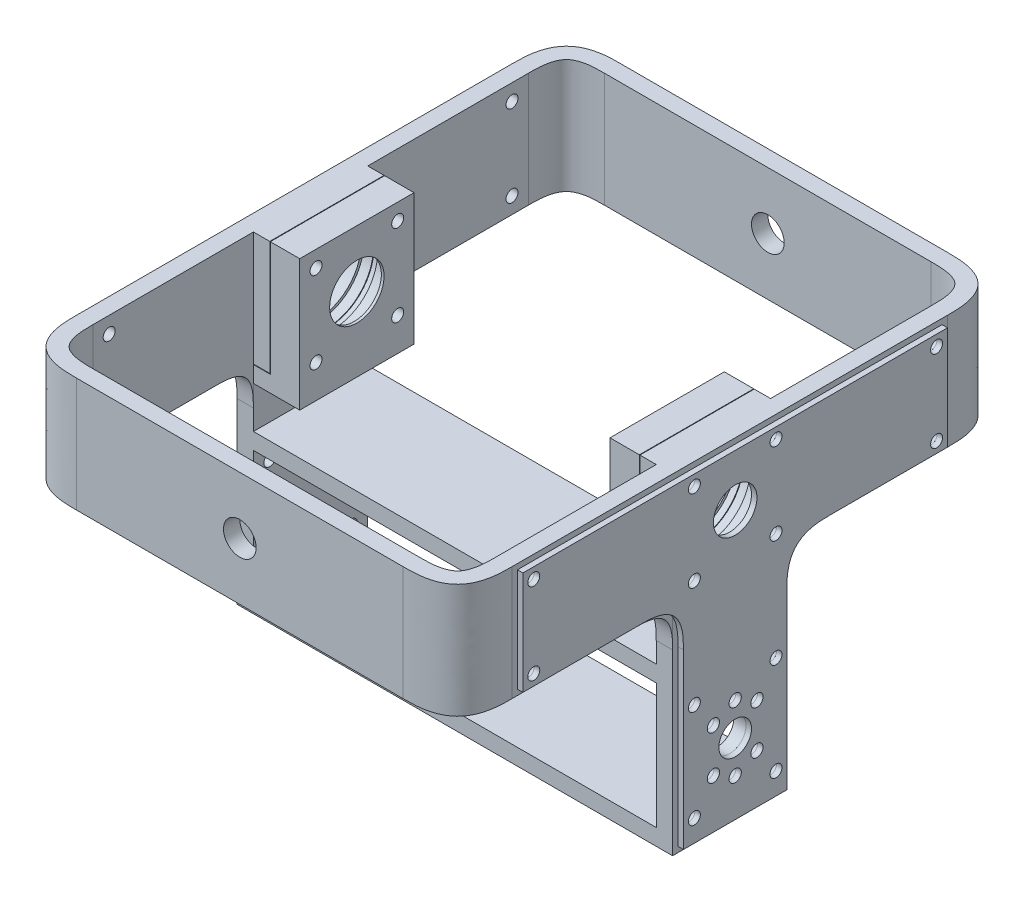
SolidWorks part; units mm, degrees
ref_plane "Front Plane" through (0, 0, 0) normal (0, 0, 1) x (1, 0, 0)
ref_plane "Top Plane" through (0, 0, 0) normal (0, 1, 0) x (1, 0, 0)
ref_plane "Right Plane" through (0, 0, 0) normal (1, 0, 0) x (0, 0, -1)
sketch "Sketch1" plane through (0, 0, 0) normal (0, 1, 0) x (1, 0, 0)
  line L1 (-80, 100) -> (80, 100)
  line L2 (-80, 100) -> (-80, -100)
  line L3 (-80, -100) -> (80, -100)
  line L4 (80, 100) -> (80, -100)
  point P4 (0, 100)
  point P6 (-80, 0)
  dimension "D1" = 200
  dimension "D2" = 160
extrude "Boss-Extrude1" add sketch "Sketch1" along normal mid plane 42
fillet "Fillet1" radius 20 4 edges at (-80, 0, 100) (80, 0, 100) (80, 0, -100) (-80, 0, -100) curvature continuous yes
sketch "Sketch2" plane through (0, 21, 0) normal (0, 1, 0) x (1, 0, 0)
  line L8 (-74, 80) -> (-74, -80)
  line L9 (-60, -94) -> (60, -94)
  line L10 (74, -80) -> (74, 80)
  line L11 (60, 94) -> (-60, 94)
  line L12 (-74, 80) -> (-74, -80)
  line L13 (-60, -94) -> (60, -94)
  line L14 (74, -80) -> (74, 80)
  line L15 (60, 94) -> (-60, 94)
  spline S9 degree 3 poles (-2071.4213, -155.8183) (-19.6568, -2.3852) (-75.4784, -45.3495) (-73.9199, -83.9583) (-73.84, -84.9423) (-73.6075, -86.4078) (-73.5109, -86.8945) (-73.2666, -87.8632) (-73.1188, -88.345) (-72.7604, -89.2755) (-72.5497, -89.7272) (-72.1629, -90.3744) (-72.0222, -90.5842) (-71.7196, -90.981) (-71.557, -91.1692) (-71.0313, -91.6999) (-70.625, -92.0093) (-69.7725, -92.5262) (-69.3225, -92.7397) (-68.3895, -93.1039) (-67.9093, -93.253) (-66.9456, -93.4997) (-66.4592, -93.5979) (-64.9892, -93.8351) (-63.9932, -93.9178) (-25.3456, -95.5031) (13.5346, -39.2005) (7.5566, -2091.7952) knots -4.636062 -4.636062 -4.636062 -4.636062 0.125 0.125 0.25 0.25 0.3125 0.3125 0.375 0.375 0.4375 0.4375 0.46875 0.46875 0.5 0.5 0.5625 0.5625 0.625 0.625 0.6875 0.6875 0.75 0.75 0.875 0.875 5.591292 5.591292 5.591292 5.591292 only from (-74, -80) to (-60, -94)
  spline S10 degree 3 poles (135.8183, -2091.4213) (-17.6148, -39.6568) (25.3495, -95.4784) (63.9583, -93.9199) (64.9423, -93.84) (66.4078, -93.6075) (66.8945, -93.5109) (67.8632, -93.2666) (68.345, -93.1188) (69.2755, -92.7604) (69.7272, -92.5497) (70.3744, -92.1629) (70.5842, -92.0222) (70.981, -91.7196) (71.1692, -91.557) (71.6999, -91.0313) (72.0093, -90.625) (72.5262, -89.7725) (72.7397, -89.3225) (73.1039, -88.3895) (73.253, -87.9093) (73.4997, -86.9456) (73.5979, -86.4592) (73.8351, -84.9892) (73.9178, -83.9932) (75.5031, -45.3456) (19.2005, -6.4654) (2071.7952, -12.4434) knots -4.636062 -4.636062 -4.636062 -4.636062 0.125 0.125 0.25 0.25 0.3125 0.3125 0.375 0.375 0.4375 0.4375 0.46875 0.46875 0.5 0.5 0.5625 0.5625 0.625 0.625 0.6875 0.6875 0.75 0.75 0.875 0.875 5.591292 5.591292 5.591292 5.591292 only from (60, -94) to (74, -80)
  spline S11 degree 3 poles (2071.4213, 155.8183) (19.6568, 2.3852) (75.4784, 45.3495) (73.9199, 83.9583) (73.84, 84.9423) (73.6075, 86.4078) (73.5109, 86.8945) (73.2666, 87.8632) (73.1188, 88.345) (72.7604, 89.2755) (72.5497, 89.7272) (72.1629, 90.3744) (72.0222, 90.5842) (71.7196, 90.981) (71.557, 91.1692) (71.0313, 91.6999) (70.625, 92.0093) (69.7725, 92.5262) (69.3225, 92.7397) (68.3895, 93.1039) (67.9093, 93.253) (66.9456, 93.4997) (66.4592, 93.5979) (64.9892, 93.8351) (63.9932, 93.9178) (25.3456, 95.5031) (-13.5346, 39.2005) (-7.5566, 2091.7952) knots -4.636062 -4.636062 -4.636062 -4.636062 0.125 0.125 0.25 0.25 0.3125 0.3125 0.375 0.375 0.4375 0.4375 0.46875 0.46875 0.5 0.5 0.5625 0.5625 0.625 0.625 0.6875 0.6875 0.75 0.75 0.875 0.875 5.591292 5.591292 5.591292 5.591292 only from (74, 80) to (60, 94)
  spline S12 degree 3 poles (-135.8183, 2091.4213) (17.6148, 39.6568) (-25.3495, 95.4784) (-63.9583, 93.9199) (-64.9423, 93.84) (-66.4078, 93.6075) (-66.8945, 93.5109) (-67.8632, 93.2666) (-68.345, 93.1188) (-69.2755, 92.7604) (-69.7272, 92.5497) (-70.3744, 92.1629) (-70.5842, 92.0222) (-70.981, 91.7196) (-71.1692, 91.557) (-71.6999, 91.0313) (-72.0093, 90.625) (-72.5262, 89.7725) (-72.7397, 89.3225) (-73.1039, 88.3895) (-73.253, 87.9093) (-73.4997, 86.9456) (-73.5979, 86.4592) (-73.8351, 84.9892) (-73.9178, 83.9932) (-75.5031, 45.3456) (-19.2005, 6.4654) (-2071.7952, 12.4434) knots -4.636062 -4.636062 -4.636062 -4.636062 0.125 0.125 0.25 0.25 0.3125 0.3125 0.375 0.375 0.4375 0.4375 0.46875 0.46875 0.5 0.5 0.5625 0.5625 0.625 0.625 0.6875 0.6875 0.75 0.75 0.875 0.875 5.591292 5.591292 5.591292 5.591292 only from (-60, 94) to (-74, 80)
  spline S13 degree 3 poles (-74, -80) (-74, -80.9914) (-73.9997, -81.9829) (-73.9199, -83.9583) (-73.84, -84.9423) (-73.6075, -86.4078) (-73.5109, -86.8945) (-73.2666, -87.8632) (-73.1188, -88.345) (-72.7604, -89.2755) (-72.5497, -89.7272) (-72.1629, -90.3744) (-72.0222, -90.5842) (-71.7196, -90.981) (-71.557, -91.1692) (-71.0313, -91.6999) (-70.625, -92.0093) (-69.7725, -92.5262) (-69.3225, -92.7397) (-68.3895, -93.1039) (-67.9093, -93.253) (-66.9456, -93.4997) (-66.4592, -93.5979) (-64.9892, -93.8351) (-63.9932, -93.9178) (-61.9975, -93.9997) (-60.9987, -94) (-60, -94) knots 0 0 0 0 0.125 0.125 0.25 0.25 0.3125 0.3125 0.375 0.375 0.4375 0.4375 0.46875 0.46875 0.5 0.5 0.5625 0.5625 0.625 0.625 0.6875 0.6875 0.75 0.75 0.875 0.875 1 1 1 1
  spline S14 degree 3 poles (60, -94) (60.9914, -94) (61.9829, -93.9997) (63.9583, -93.9199) (64.9423, -93.84) (66.4078, -93.6075) (66.8945, -93.5109) (67.8632, -93.2666) (68.345, -93.1188) (69.2755, -92.7604) (69.7272, -92.5497) (70.3744, -92.1629) (70.5842, -92.0222) (70.981, -91.7196) (71.1692, -91.557) (71.6999, -91.0313) (72.0093, -90.625) (72.5262, -89.7725) (72.7397, -89.3225) (73.1039, -88.3895) (73.253, -87.9093) (73.4997, -86.9456) (73.5979, -86.4592) (73.8351, -84.9892) (73.9178, -83.9932) (73.9997, -81.9975) (74, -80.9987) (74, -80) knots 0 0 0 0 0.125 0.125 0.25 0.25 0.3125 0.3125 0.375 0.375 0.4375 0.4375 0.46875 0.46875 0.5 0.5 0.5625 0.5625 0.625 0.625 0.6875 0.6875 0.75 0.75 0.875 0.875 1 1 1 1
  spline S15 degree 3 poles (74, 80) (74, 80.9914) (73.9997, 81.9829) (73.9199, 83.9583) (73.84, 84.9423) (73.6075, 86.4078) (73.5109, 86.8945) (73.2666, 87.8632) (73.1188, 88.345) (72.7604, 89.2755) (72.5497, 89.7272) (72.1629, 90.3744) (72.0222, 90.5842) (71.7196, 90.981) (71.557, 91.1692) (71.0313, 91.6999) (70.625, 92.0093) (69.7725, 92.5262) (69.3225, 92.7397) (68.3895, 93.1039) (67.9093, 93.253) (66.9456, 93.4997) (66.4592, 93.5979) (64.9892, 93.8351) (63.9932, 93.9178) (61.9975, 93.9997) (60.9987, 94) (60, 94) knots 0 0 0 0 0.125 0.125 0.25 0.25 0.3125 0.3125 0.375 0.375 0.4375 0.4375 0.46875 0.46875 0.5 0.5 0.5625 0.5625 0.625 0.625 0.6875 0.6875 0.75 0.75 0.875 0.875 1 1 1 1
  spline S16 degree 3 poles (-60, 94) (-60.9914, 94) (-61.9829, 93.9997) (-63.9583, 93.9199) (-64.9423, 93.84) (-66.4078, 93.6075) (-66.8945, 93.5109) (-67.8632, 93.2666) (-68.345, 93.1188) (-69.2755, 92.7604) (-69.7272, 92.5497) (-70.3744, 92.1629) (-70.5842, 92.0222) (-70.981, 91.7196) (-71.1692, 91.557) (-71.6999, 91.0313) (-72.0093, 90.625) (-72.5262, 89.7725) (-72.7397, 89.3225) (-73.1039, 88.3895) (-73.253, 87.9093) (-73.4997, 86.9456) (-73.5979, 86.4592) (-73.8351, 84.9892) (-73.9178, 83.9932) (-73.9997, 81.9975) (-74, 80.9987) (-74, 80) knots 0 0 0 0 0.125 0.125 0.25 0.25 0.3125 0.3125 0.375 0.375 0.4375 0.4375 0.46875 0.46875 0.5 0.5 0.5625 0.5625 0.625 0.625 0.6875 0.6875 0.75 0.75 0.875 0.875 1 1 1 1
extrude "Cut-Extrude1" cut sketch "Sketch2" against normal through all
sketch "Sketch8" plane through (0, 0, 0) normal (0, 1, 0) x (1, 0, 0)
  line L0 (74, -80) -> (74, 80) construction
  line L1 (68, 21) -> (74, 21)
  line L2 (68, 21) -> (68, -21)
  line L3 (68, -21) -> (74, -21)
  line L4 (74, 21) -> (74, -21)
  point P6 (68, 0)
  dimension "D1" = 42
  dimension "D2" = 6
extrude "Boss-Extrude3" add sketch "Sketch8" along normal mid plane 42
mirror "Mirror1" about plane through (0, 0, 0) normal (1, 0, 0) of "Boss-Extrude3"
sketch "Sketch3" plane through (0, 0, 0) normal (0, 0, 1) x (1, 0, 0)
  line L0 (-67.8, 21) -> (-67.8, -21.2)
  line L1 (-67.8, -21.2) -> (-80, -21.2)
  line L2 (-80, -21.2) -> (-80, -100.5)
  line L3 (-80, -100.5) -> (80, -100.5)
  line L4 (80, -100.5) -> (80, -21.2)
  line L5 (80, -21.2) -> (67.8, -21.2)
  line L6 (67.8, -21.2) -> (67.8, 21)
  line L7 (67.8, 21) -> (57, 21)
  line L8 (57, 21) -> (57, -27.2)
  line L12 (-57, -27.2) -> (-57, 21)
  line L13 (-57, 21) -> (-67.8, 21)
  line L14 (-74, -94.5) -> (74, -94.5)
  line L15 (74, -94.5) -> (74, -48.5)
  line L16 (74, -48.5) -> (-74, -48.5)
  line L17 (-74, -48.5) -> (-74, -94.5)
  line L24 (-178.1537, -72.5) -> (141.3551, -72.5) construction
  line L25 (-165.0071, 0) -> (132.421, 0) construction
  line L26 (74, -42.5) -> (-74, -42.5)
  line L27 (-74, -42.5) -> (-74, -27.2)
  line L28 (-74, -27.2) -> (-57, -27.2)
  line L29 (74, -42.5) -> (74, -27.2)
  line L30 (74, -27.2) -> (57, -27.2)
  point P23 (0, -100.5)
  dimension "D1" = 160
  dimension "D2" = 6
  dimension "D3" = 6
  dimension "D6" = 12.2
  dimension "D10" = 72.5
  dimension "D11" = 24
  dimension "D12" = 22
  dimension "D13" = 6
  dimension "D5" = 42
  dimension "D15" = 21.2
  dimension "D14" = 23
  dimension "D4" = 6
  dimension "D7" = 6
extrude "Boss-Extrude2" add sketch "Sketch3" along normal mid plane 42 separate body
sketch "Sketch4" plane through (0, 0, 0) normal (1, 0, 0) x (0, 0, -1)
  circle A0 centre (0, 0) radius 6
  dimension "D1" = 12
extrude "Cut-Extrude2" cut sketch "Sketch4" against normal through all both and the other way through all
sketch "Sketch5" plane through (0, 0, 0) normal (1, 0, 0) x (0, 0, -1)
  circle A0 centre (0, -72.5) radius 6
  dimension "D2" = 12
  dimension "D1" = 72.5
extrude "Cut-Extrude3" cut sketch "Sketch5" along normal through all
sketch "Sketch6" plane through (0, 0, 0) normal (0, 0, 1) x (1, 0, 0)
  line L0 (-124.789, 0) -> (125.5541, 0) construction
  line L1 (80, 10) -> (79, 10)
  line L2 (79, 10) -> (79, 16.1)
  line L3 (79, 16.1) -> (71.5, 16.1)
  line L4 (71.5, 16.1) -> (71.5, 17.1)
  line L5 (71.5, 17.1) -> (65.5, 17.1)
  line L7 (57, 0) -> (80, 0)
  line L8 (80, 0) -> (80, 10)
  line L9 (0, 53.1317) -> (0, -45.0231) construction
  line L10 (65.5, 17.1) -> (65.5, 16.1)
  line L11 (65.5, 16.1) -> (58, 16.1)
  line L12 (58, 16.1) -> (58, 10)
  line L13 (58, 10) -> (57, 10)
  line L14 (57, 10) -> (57, 0)
  dimension "D1" = 20
  dimension "D2" = 1
  dimension "D3" = 160
  dimension "D4" = 7.5
  dimension "D5" = 6
  dimension "D6" = 32.2
  dimension "D7" = 34.2
revolve "Cut-Revolve1" cut sketch "Sketch6" angle 360 about L0
mirror "Mirror2" about plane through (0, 0, 0) normal (1, 0, 0) of "Cut-Revolve1"
sketch "Sketch10" plane through (0, 0, 0) normal (1, 0, 0) x (0, 0, -1)
  line L8 (78, 19) -> (-78, 19)
  line L9 (-78, 19) -> (-78, -19)
  line L10 (-78, -19) -> (78, -19)
  line L11 (78, -19) -> (78, 19)
  line L12 (78, 19) -> (-78, 19)
  line L13 (-78, 19) -> (-78, -19)
  line L14 (-78, -19) -> (-19, -19)
  line L15 (78, -19) -> (78, 19)
  line L16 (-19, -23.2) -> (-19, -19)
  line L17 (19, -23.2) -> (19, -19)
  line L18 (19, -19) -> (78, -19)
  line L19 (-19, -19) -> (19, -19) construction
  line L20 (19, -98.5) -> (19, -23.2)
  line L21 (19, -23.2) -> (-19, -23.2)
  line L22 (-19, -23.2) -> (-19, -98.5)
  line L23 (-19, -98.5) -> (19, -98.5)
  line L24 (19, -98.5) -> (19, -23.2)
  line L25 (19, -23.2) -> (-19, -23.2) construction
  line L26 (-19, -23.2) -> (-19, -98.5)
  line L27 (-19, -98.5) -> (19, -98.5)
  circle A0 centre (0, 0) radius 8
  circle A1 centre (0, -72.5) radius 6
  dimension "D3" = 12
  dimension "D4" = 16
  dimension "D5" = 72.5
  dimension "D2" = 2
extrude "Boss-Extrude5" add sketch "Sketch10" along normal blind 2 from offset 80 separate body
sketch "Sketch11" plane through (0, 0, 0) normal (1, 0, 0) x (0, 0, -1)
  circle A0 centre (0, -72.5) radius 18.1
  dimension "D1" = 36.2
  dimension "D2" = 72.5
extrude "Cut-Extrude4" cut sketch "Sketch11" along normal offset from surface (75.5 mm away) 6.5 up to face at (82, -29.375, 0)
sketch "Sketch12" plane through (82, 0, 0) normal (1, 0, 0) x (0, 0, -1)
  line L0 (-74, 15) -> (-74, -15) construction
  line L1 (-15, -54.5) -> (15, -54.5) construction
  line L2 (-15, -54.5) -> (-15, -90.5) construction
  line L3 (-15, -90.5) -> (15, -90.5) construction
  line L4 (15, -54.5) -> (15, -90.5) construction
  line L5 (-15, -54.5) -> (15, -90.5) construction
  line L6 (-15, -90.5) -> (15, -54.5) construction
  line L7 (-15, 15) -> (15, 15) construction
  line L8 (-15, 15) -> (-15, -15) construction
  line L9 (-15, -15) -> (15, -15) construction
  line L10 (15, 15) -> (15, -15) construction
  line L11 (-15, 15) -> (15, -15) construction
  line L12 (-15, -15) -> (15, 15) construction
  line L13 (-74, 15) -> (74, 15) construction
  line L14 (78, 19) -> (-78, 19) construction
  line L15 (-78, 19) -> (-78, -19) construction
  circle A0 centre (-15, -54.5) radius 2.2
  circle A1 centre (15, -54.5) radius 2.2
  circle A2 centre (15, -90.5) radius 2.2
  circle A3 centre (-15, -90.5) radius 2.2
  circle A4 centre (0, -72.5) radius 18 construction
  circle A5 centre (0, 0) radius 16 construction
  circle A6 centre (-15, -15) radius 2.2
  circle A7 centre (15, -15) radius 2.2
  circle A8 centre (15, 15) radius 2.2
  circle A9 centre (-15, 15) radius 2.2
  circle A10 centre (-74, 15) radius 2.2
  circle A11 centre (-74, -15) radius 2.2
  circle A12 centre (74, -15) radius 2.2
  circle A13 centre (74, 15) radius 2.2
  point P8 (0, -72.5)
  point P31 (0, 15)
  dimension "D1" = 4.4
  dimension "D2" = 36
  dimension "D4" = 32
  dimension "D3" = 36
  dimension "D5" = 30
  dimension "D6" = 4
  dimension "D7" = 4
extrude "Cut-Extrude5" cut sketch "Sketch12" against normal through all both and the other way through all
sketch "Sketch13" plane through (0, 0, 0) normal (1, 0, 0) x (0, 0, -1)
  line L0 (0, -60.5) -> (0, -84.5) construction
  line L1 (-8, -64.5) -> (8, -64.5) construction
  line L2 (-8, -64.5) -> (-8, -80.5) construction
  line L3 (-8, -80.5) -> (8, -80.5) construction
  line L4 (8, -64.5) -> (8, -80.5) construction
  line L5 (-8, -64.5) -> (8, -80.5) construction
  line L6 (-8, -80.5) -> (8, -64.5) construction
  circle A0 centre (0, -72.5) radius 6 construction
  circle A1 centre (0, -72.5) radius 6 construction
  circle A2 centre (-8, -64.5) radius 2.25
  circle A3 centre (8, -64.5) radius 2.25
  circle A4 centre (0, -60.5) radius 2.25
  circle A5 centre (0, -84.5) radius 2.25
  circle A6 centre (8, -80.5) radius 2.25
  circle A7 centre (-8, -80.5) radius 2.25
  point P9 (0, -72.5)
  dimension "D1" = 4.5
  dimension "D2" = 16
  dimension "D3" = 24
extrude "Cut-Extrude6" cut sketch "Sketch13" along normal through all
fillet "Fillet7" radius 16 2 edges at (81, -19, -19) (81, -19, 19) curvature continuous yes
sketch "Sketch15" plane through (-80, 0, 0) normal (-1, 0, 0) x (0, 0, 1)
  line L16 (-80, -21) -> (80, -21) construction
  line L17 (-35, -21) -> (-21, -21)
  line L18 (-21, -35) -> (-21, -21)
  line L19 (21, -35) -> (21, -21)
  line L20 (-80, -21) -> (-35, -21) construction
  line L21 (35, -21) -> (80, -21) construction
  line L22 (21, -21) -> (35, -21)
  line L23 (-21, -21) -> (21, -21) construction
  line L24 (35, -21) -> (80, -21)
  line L25 (21, -100.5) -> (21, -35)
  line L26 (-21, -100.5) -> (21, -100.5)
  line L27 (-21, -35) -> (-21, -100.5)
  line L28 (-80, -21) -> (-35, -21)
  line L29 (-80, 21) -> (-80, -21)
  line L30 (80, 21) -> (-80, 21)
  line L31 (80, -21) -> (80, 21)
  line L32 (35, -21) -> (80, -21) construction
  line L33 (21, -100.5) -> (21, -35) construction
  line L34 (-21, -100.5) -> (21, -100.5) construction
  line L35 (-21, -35) -> (-21, -100.5) construction
  line L36 (-80, -21) -> (-35, -21)
  line L37 (-80, 21) -> (-80, -21) construction
  line L38 (80, 21) -> (-80, 21) construction
  line L39 (80, -21) -> (80, 21) construction
  spline S4 degree 3 poles (-2974.6377, 63.5796) (82.49, -148.069) (20.1334, -88.0483) (21.0185, -33.0463) (21.0306, -32.5585) (21.0808, -31.5852) (21.1215, -31.0999) (21.2347, -30.1321) (21.3081, -29.6497) (21.4992, -28.6887) (21.6178, -28.208) (21.906, -27.2697) (22.076, -26.8106) (22.4817, -25.918) (22.7201, -25.481) (23.2655, -24.6661) (23.5727, -24.2865) (24.0924, -23.7648) (24.2765, -23.598) (24.6584, -23.2852) (24.8557, -23.1392) (25.4653, -22.7292) (25.895, -22.4933) (26.7925, -22.083) (27.2542, -21.9116) (28.1871, -21.6235) (28.6602, -21.5059) (29.6171, -21.3137) (30.101, -21.239) (31.0771, -21.1235) (31.5669, -21.0821) (32.5467, -21.0309) (33.0371, -21.0187) (87.9144, -20.1312) (144.7647, -82.3629) (79.7976, 2975.9853) knots -6.917192 -6.917192 -6.917192 -6.917192 0.0625 0.0625 0.125 0.125 0.1875 0.1875 0.25 0.25 0.3125 0.3125 0.375 0.375 0.4375 0.4375 0.5 0.5 0.53125 0.53125 0.5625 0.5625 0.625 0.625 0.6875 0.6875 0.75 0.75 0.8125 0.8125 0.875 0.875 0.9375 0.9375 7.866208 7.866208 7.866208 7.866208 only from (21, -35) to (35, -21)
  spline S5 degree 3 poles (63.5796, 2974.6377) (-148.069, -82.49) (-88.0483, -20.1334) (-33.0463, -21.0185) (-32.5585, -21.0306) (-31.5852, -21.0808) (-31.0999, -21.1215) (-30.1321, -21.2347) (-29.6497, -21.3081) (-28.6887, -21.4992) (-28.208, -21.6178) (-27.2697, -21.906) (-26.8106, -22.076) (-25.918, -22.4817) (-25.481, -22.7201) (-24.6661, -23.2655) (-24.2865, -23.5727) (-23.7648, -24.0924) (-23.598, -24.2765) (-23.2852, -24.6584) (-23.1392, -24.8557) (-22.7292, -25.4653) (-22.4933, -25.895) (-22.083, -26.7925) (-21.9116, -27.2542) (-21.6235, -28.1871) (-21.5059, -28.6602) (-21.3137, -29.6171) (-21.239, -30.101) (-21.1235, -31.0771) (-21.0821, -31.5669) (-21.0309, -32.5467) (-21.0187, -33.0371) (-20.1312, -87.9144) (-82.3629, -144.7647) (2975.9853, -79.7976) knots -6.917192 -6.917192 -6.917192 -6.917192 0.0625 0.0625 0.125 0.125 0.1875 0.1875 0.25 0.25 0.3125 0.3125 0.375 0.375 0.4375 0.4375 0.5 0.5 0.53125 0.53125 0.5625 0.5625 0.625 0.625 0.6875 0.6875 0.75 0.75 0.8125 0.8125 0.875 0.875 0.9375 0.9375 7.866208 7.866208 7.866208 7.866208 only from (-35, -21) to (-21, -35)
  spline S6 degree 3 poles (21, -35) (21, -34.5112) (21.0028, -34.0226) (21.0185, -33.0463) (21.0306, -32.5585) (21.0808, -31.5852) (21.1215, -31.0999) (21.2347, -30.1321) (21.3081, -29.6497) (21.4992, -28.6887) (21.6178, -28.208) (21.906, -27.2697) (22.076, -26.8106) (22.4817, -25.918) (22.7201, -25.481) (23.2655, -24.6661) (23.5727, -24.2865) (24.0924, -23.7648) (24.2765, -23.598) (24.6584, -23.2852) (24.8557, -23.1392) (25.4653, -22.7292) (25.895, -22.4933) (26.7925, -22.083) (27.2542, -21.9116) (28.1871, -21.6235) (28.6602, -21.5059) (29.6171, -21.3137) (30.101, -21.239) (31.0771, -21.1235) (31.5669, -21.0821) (32.5467, -21.0309) (33.0371, -21.0187) (34.0183, -21.0028) (34.5091, -21) (35, -21) knots 0 0 0 0 0.0625 0.0625 0.125 0.125 0.1875 0.1875 0.25 0.25 0.3125 0.3125 0.375 0.375 0.4375 0.4375 0.5 0.5 0.53125 0.53125 0.5625 0.5625 0.625 0.625 0.6875 0.6875 0.75 0.75 0.8125 0.8125 0.875 0.875 0.9375 0.9375 1 1 1 1
  spline S7 degree 3 poles (-35, -21) (-34.5112, -21) (-34.0226, -21.0028) (-33.0463, -21.0185) (-32.5585, -21.0306) (-31.5852, -21.0808) (-31.0999, -21.1215) (-30.1321, -21.2347) (-29.6497, -21.3081) (-28.6887, -21.4992) (-28.208, -21.6178) (-27.2697, -21.906) (-26.8106, -22.076) (-25.918, -22.4817) (-25.481, -22.7201) (-24.6661, -23.2655) (-24.2865, -23.5727) (-23.7648, -24.0924) (-23.598, -24.2765) (-23.2852, -24.6584) (-23.1392, -24.8557) (-22.7292, -25.4653) (-22.4933, -25.895) (-22.083, -26.7925) (-21.9116, -27.2542) (-21.6235, -28.1871) (-21.5059, -28.6602) (-21.3137, -29.6171) (-21.239, -30.101) (-21.1235, -31.0771) (-21.0821, -31.5669) (-21.0309, -32.5467) (-21.0187, -33.0371) (-21.0028, -34.0183) (-21, -34.5091) (-21, -35) knots 0 0 0 0 0.0625 0.0625 0.125 0.125 0.1875 0.1875 0.25 0.25 0.3125 0.3125 0.375 0.375 0.4375 0.4375 0.5 0.5 0.53125 0.53125 0.5625 0.5625 0.625 0.625 0.6875 0.6875 0.75 0.75 0.8125 0.8125 0.875 0.875 0.9375 0.9375 1 1 1 1
  line M20 (-80, -21) -> (80, -21)
extrude "Boss-Extrude7" add sketch "Sketch15" against normal blind 6 contours S7 L18 M20 | L19 S6 M20 region at (-80, -23.4283, -23.4291) region at (-80, -23.429, 23.4291)
mirror "Mirror9" about plane through (0, 0, 0) normal (1, 0, 0) of "Boss-Extrude7"
sketch "Sketch16" plane through (0, 0, 0) normal (0, 0, 1) x (1, 0, 0)
  circle A0 centre (0, 0) radius 6
  dimension "D1" = 12
extrude "Cut-Extrude7" cut sketch "Sketch16" against normal through all both and the other way through all
equation "\"width\"= 160mm"
equation "\"depth\"= 200mm"
equation "\"wall_thickness\"= 6mm"
equation "\"height\"= 42mm"
equation "\"aluminum_thickness\"= 2mm"
equation "\"D1@Sketch1\"=\"depth\""
equation "\"D2@Sketch1\"=\"width\""
equation "\"D1@Boss-Extrude1\"=\"height\""
equation "\"D1@Sketch2\"=\"wall_thickness\""
equation "\"D1@Sketch3\"=\"width\""
equation "\"D2@Sketch3\"=\"wall_thickness\""
equation "\"D3@Sketch3\"=\"wall_thickness\""
equation "\"D6@Sketch3\"=(\"wall_thickness\"*2)+0.2mm"
equation "\"motor_center_distance_to_axle\" = 72.5mm"
equation "\"D10@Sketch3\"=\"motor_center_distance_to_axle\""
equation "\"D13@Sketch3\"=\"wall_thickness\""
equation "\"D1@Boss-Extrude2\"=\"height\""
equation "\"D5@Sketch3\"=\"height\""
equation "\"D15@Sketch3\"=(\"height\"/2)+0.2mm"
equation "\"D1@Sketch5\"=\"motor_center_distance_to_axle\""
equation "\"D3@Sketch6\"=\"width\""
equation "\"D1@Sketch8\"=\"height\""
equation "\"D2@Sketch8\"=\"wall_thickness\""
equation "\"D1@Boss-Extrude3\"=\"height\""
equation "\"D4@Sketch3\"=\"wall_thickness\""
equation "\"D7@Sketch3\"=\"wall_thickness\""
equation "\"aluminum_offset\"= 2mm"
equation "\"D2@Sketch10\"=\"aluminum_offset\""
equation "\"D1@Sketch10\"=\"aluminum_offset\""
equation "\"D5@Sketch10\"=\"motor_center_distance_to_axle\""
equation "\"D1@Boss-Extrude5\"=\"aluminum_thickness\""
equation "\"D19@Boss-Extrude5\"=\"width\"/2"
equation "\"D2@Sketch11\"=\"motor_center_distance_to_axle\""
equation "\"D1@Sketch15\"=\"aluminum_offset\""
equation "\"D1@Boss-Extrude7\"=\"wall_thickness\""
